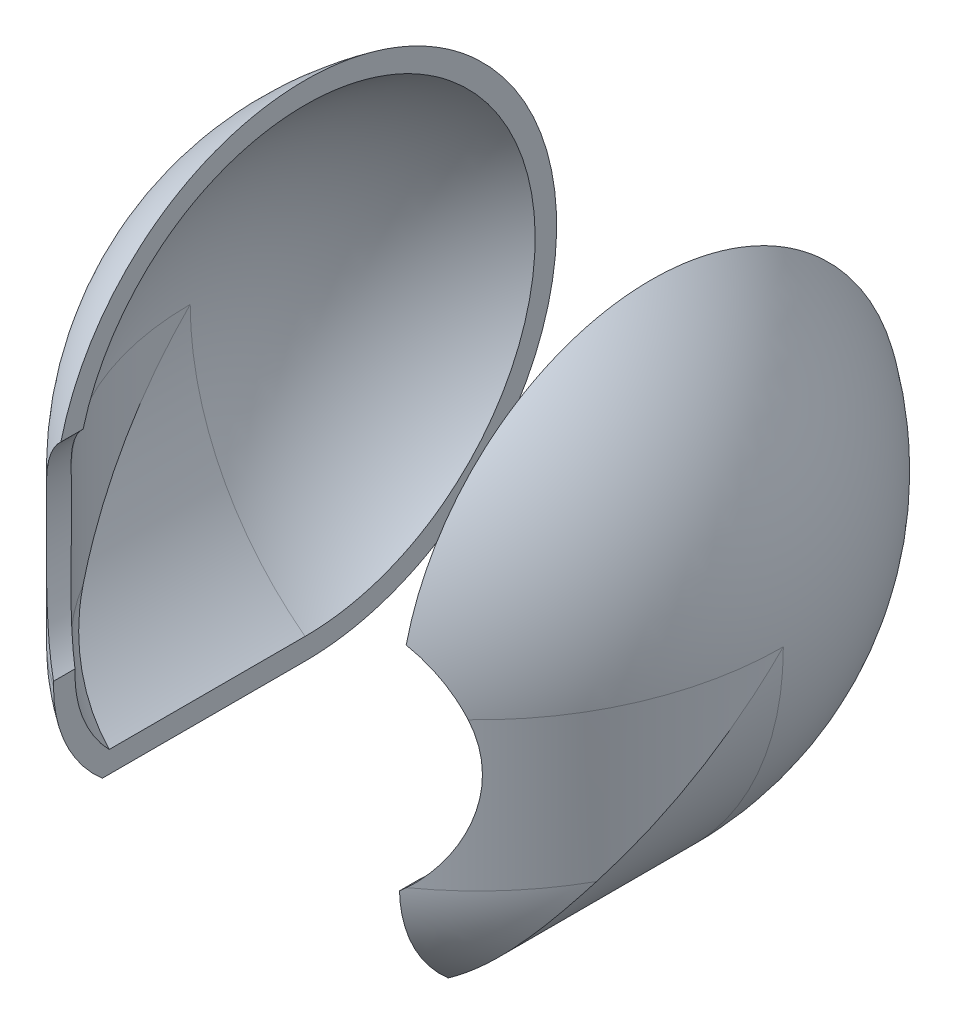
SolidWorks part; units mm, degrees
ref_plane "Alzado" through (0, 0, 0) normal (0, 0, 1) x (1, 0, 0)
ref_plane "Planta" through (0, 0, 0) normal (0, 1, 0) x (1, 0, 0)
ref_plane "Vista lateral" through (0, 0, 0) normal (1, 0, 0) x (0, 0, -1)
sketch "Croquis1" plane through (0, 0, 0) normal (0, 0, 1) x (1, 0, 0)
  line L0 (0, 35) -> (0, -35)
  arc A0 (0, 35) -> (0, -35) centre (0, 0) ccw
revolve "Revolución1" add sketch "Croquis1" angle 360 about L0 other way angle 360
sketch "Croquis3" plane through (0, 0, 0) normal (0, 0, 1) x (1, 0, 0)
  line L0 (0, 16.9366) -> (0, 6.4344)
  line L1 (0, 0) -> (35, 0)
  line L2 (0, 0) -> (0, -35)
  line L3 (0, -35) -> (17, -35)
  line L4 (35, 0) -> (35, -17)
  arc A0 (35, -17) -> (17, -35) centre (17, -17) cw
  dimension "D1" = 18
revolve "Revolución18" add sketch "Croquis3" angle 180 about L2 region at (16.6889, -16.6889, 0)
sketch "Croquis4" plane through (0, 0, 0) normal (0, 0, 1) x (1, 0, 0)
  circle A0 centre (0, 0) radius 42.0416
  circle A1 centre (0, 0) radius 35
extrude "Cortar-Extruir1" cut sketch "Croquis4" along normal blind 53
sketch "Croquis5" plane through (0, 0, 0) normal (0, 0, 1) x (1, 0, 0)
  line L2 (-22, 31.1367) -> (-19.83, 31.1367)
  line L4 (-22, 31.1367) -> (-36.6096, 31.1367)
  line L6 (-22, -33.3554) -> (-36.6096, -33.3554)
  line L7 (-36.6096, 31.1367) -> (-36.6096, -33.3554)
  line L8 (22, 31.1367) -> (35, 31.1367)
  line L9 (-22, -33.3554) -> (-19.83, -33.3554)
  line L10 (22, -36.1659) -> (35, -36.1659)
  line L11 (35, 31.1367) -> (35, -36.1659)
  line L12 (22, -36.1659) -> (-19.83, -36.1659)
  line L13 (22, 31.1367) -> (19.83, 31.1367)
  line L14 (19.83, 36.6364) -> (-19.83, 36.6364)
  line L18 (-19.83, 36.6364) -> (19.83, 36.6364)
  line L19 (-19.83, 36.6364) -> (-19.83, -36.1659)
  line L20 (-19.83, -36.1659) -> (19.83, -36.1659)
  line L21 (19.83, 36.6364) -> (19.83, -36.1659)
sketch "Croquis6" plane through (0, 0, 0) normal (0, 0, 1) x (1, 0, 0)
  line L0 (-34.7269, -4.3636) -> (-16.7269, -4.3636)
  line L1 (34.7543, -4.1399) -> (16.7543, -4.1399)
  arc A0 (-35, 0) -> (-30.5941, -17) centre (0, 0) ccw construction
  arc A1 (30.5941, -17) -> (35, 0) centre (0, 0) ccw construction
  ellipse E0 centre (-16.7269, -4.3636) end of major axis (-16.7269, 9.6364) minor radius 11
  ellipse E1 centre (16.7543, -4.1399) end of major axis (16.7543, -18.1399) minor radius 11
extrude "Cortar-Extruir4" cut sketch "Croquis5" against normal blind 38 and the other way blind 38 contours L12 L14 region at (0, 0.2353, 0)
shell "Vaciado3" thickness 2 removed face at (-19.83, -6.0348, -1.2905)
shell "Vaciado4" thickness 2 removed face at (19.83, -6.0348, -1.2905)
sketch "Croquis8" plane through (25.3401, 3.698, -6.7717) normal (0, 0, 1) x (1, 0, 0)
  line L0 (-45.1701, -20.698) -> (-45.1701, -3.698) construction
  line L1 (-45.1701, -32.5384) -> (-45.1701, 25.1425) construction
  line L2 (-45.1701, 3.2226) -> (-45.1701, -20.1089)
  spline S0 degree 3 poles (-45.1701, -20.1089) (-47.2647, -18.2737) (-49.3582, -14.2824) (-50.3574, -5.6838) (-48.3923, 0.2217) (-45.1701, 3.2226) knots 0 0 0 0 0.319266 0.506234 1 1 1 1
  spline S1 degree 3 number of poles 824 (-39.1107, 5.5964) -> (-39.3361, -22.4027) construction
extrude "Cortar-Extruir5" cut sketch "Croquis8" along normal blind 44
sketch "Croquis11" plane through (25.3401, 3.698, -6.7717) normal (0, 0, 1) x (1, 0, 0)
  line L0 (-5.5101, -20.698) -> (-5.5101, -32.5384) construction
  line L1 (-5.5101, 22.6795) -> (-5.5101, -30.0755) construction
  line L2 (-5.5101, 25.1425) -> (-5.5101, -32.5384) construction
  line L3 (-5.5101, 2.9287) -> (-5.5101, -21.0897)
  spline S0 degree 3 poles (-5.5101, -21.0897) (-3.3802, -19.4432) (-0.7928, -15.11) (0.2265, -6.054) (-2.2355, 0.2688) (-5.5101, 2.9287) knots 0 0 0 0 0.29719 0.54021 1 1 1 1
  spline S1 degree 3 number of poles 825 (-10.9681, -23.0287) -> (-11.1865, 4.97) construction
extrude "Cortar-Extruir11" cut sketch "Croquis11" along normal blind 50
